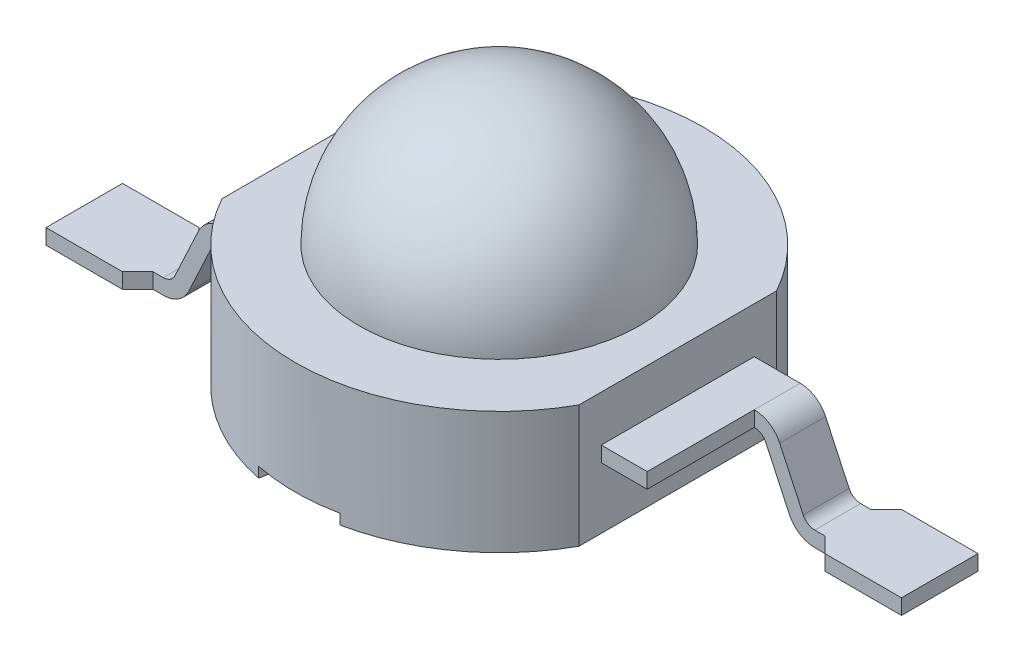
SolidWorks part; units mm, degrees
material "ABS PC"
ref_plane "Front Plane" through (0, 0, 0) normal (0, 0, 1) x (1, 0, 0)
ref_plane "Top Plane" through (0, 0, 0) normal (0, 1, 0) x (1, 0, 0)
ref_plane "Right Plane" through (0, 0, 0) normal (1, 0, 0) x (0, 0, -1)
sketch "Sketch1" plane through (0, 0, 0) normal (0, 1, 0) x (1, 0, 0)
  line L1 (-3.5, 1.9365) -> (3.5, 1.9365) construction
  line L2 (-3.5, 1.9365) -> (-3.5, -1.9365)
  line L3 (-3.5, -1.9365) -> (3.5, -1.9365) construction
  line L4 (3.5, 1.9365) -> (3.5, -1.9365)
  arc A0 (-3.5, -1.9365) -> (3.5, -1.9365) centre (0, 0) ccw
  arc A1 (3.5, 1.9365) -> (-3.5, 1.9365) centre (0, 0) ccw
  dimension "D1" = 8
  dimension "D2" = 7
extrude "Boss-Extrude1" add sketch "Sketch1" along normal blind 2.4
sketch "Sketch2" plane through (0, 0, 0) normal (0, 1, 0) x (1, 0, 0)
  circle A0 centre (0, 0) radius 2.75
  dimension "D1" = 5.5
extrude "Boss-Extrude2" add sketch "Sketch2" against normal blind 0.25
sketch "Sketch3" plane through (0, 2.4, 0) normal (0, 1, 0) x (1, 0, 0)
  circle A0 centre (0, 0) radius 2
  dimension "D1" = 4
extrude "Boss-Extrude3" add sketch "Sketch3" along normal blind 0.3
sketch "Sketch4" plane through (0, 0, 0) normal (0, 0, 1) x (1, 0, 0)
  line L0 (0, 2.4) -> (0, 5.15)
  line L1 (3.5, 2.4) -> (-3.5, 2.4) construction
  line L2 (2.75, 2.4) -> (0, 2.4)
  arc A0 (2.75, 2.4) -> (0, 5.15) centre (0, 2.4) ccw
  dimension "D2" = 2.75
revolve "Revolve1" add sketch "Sketch4" angle 360 about L0
ref_plane "Plane1" through (0, 1.35, 0) normal (0, 1, 0) x (-1, 0, 0)
sketch "Sketch5" plane through (0, 1.35, 0) normal (0, 1, 0) x (-1, 0, 0)
  line L1 (-4.4, 1.5) -> (3.9, 1.5)
  line L2 (-4.4, 1.5) -> (-4.4, -1.5)
  line L3 (-4.4, -1.5) -> (3.9, -1.5)
  line L4 (3.9, 1.5) -> (3.9, -1.5)
  dimension "D1" = 8.3
  dimension "D2" = 3
extrude "Boss-Extrude4" add sketch "Sketch5" along normal mid plane 0.3
sketch "Sketch6" plane through (4.4, 0, 0) normal (1, 0, 0) x (0, 0, -1)
  line L0 (-1.5, 1.2) -> (1.5, 1.2) construction
  line L1 (1.5, 1.5) -> (0.6, 1.5)
  line L2 (1.5, 1.5) -> (1.5, 1.2)
  line L3 (1.5, 1.2) -> (0.6, 1.2)
  line L4 (0.6, 1.5) -> (0.6, 1.2)
  line L5 (1.05, 1.5) -> (1.05, 1.2) construction
  line L6 (1.05, 1.2) -> (0.6, 1.35) construction
  line L7 (0.6, 1.35) -> (1.05, 1.35) construction
  dimension "D1" = 0.9
ref_plane "Plane2" through (0, 0, -1.05) normal (0, 0, 1) x (1, 0, 0)
sketch "Sketch7" plane through (0, 0, -1.05) normal (0, 0, 1) x (1, 0, 0)
  line L0 (4.4, 1.2) -> (4.4, 1.35) construction
  line L1 (4.7625, 1.119) -> (5.2233, 0.131)
  line L2 (3.5, 1.2) -> (4.4, 1.2) construction
  line L3 (-2.75, -0.25) -> (2.75, -0.25) construction
  line L4 (5.5858, -0.1) -> (5.7858, -0.1)
  arc A0 (4.4, 1.35) -> (4.7625, 1.119) centre (4.4, 0.95) cw
  arc A1 (5.2233, 0.131) -> (5.5858, -0.1) centre (5.5858, 0.3) ccw
  point P16 (5.331, -0.1)
  dimension "D5" = 0.4
  dimension "D1" = 115
  dimension "D2" = 0.15
  dimension "D3" = 0.4
  dimension "D4" = 0.2
sweep "Sweep2" add profiles "Sketch6" path "Sketch7"
sketch "Sketch8" plane through (-3.9, 0, 0) normal (-1, 0, 0) x (0, 0, 1)
  line L0 (-1.5, 1.2) -> (1.5, 1.2) construction
  line L1 (1.5, 1.5) -> (0.6, 1.5)
  line L2 (1.5, 1.5) -> (1.5, 1.2)
  line L3 (1.5, 1.2) -> (0.6, 1.2)
  line L4 (0.6, 1.5) -> (0.6, 1.2)
  line L5 (1.05, 1.5) -> (1.05, 1.2) construction
  line L6 (1.05, 1.2) -> (0.6, 1.35) construction
  line L7 (0.6, 1.35) -> (1.05, 1.35) construction
  dimension "D1" = 0.9
ref_plane "Plane3" through (0, 0, 1.05) normal (0, 0, 1) x (1, 0, 0)
sketch "Sketch9" plane through (0, 0, 1.05) normal (0, 0, 1) x (1, 0, 0)
  line L0 (-3.9, 1.5) -> (-3.9, 1.2) construction
  line L1 (-4.2625, 1.119) -> (-4.7233, 0.131)
  line L3 (-3.5, 1.2) -> (-3.9, 1.2) construction
  line L4 (-5.0858, -0.1) -> (-5.2858, -0.1)
  line L5 (-2.75, -0.25) -> (2.75, -0.25) construction
  arc A0 (-3.9, 1.35) -> (-4.2625, 1.119) centre (-3.9, 0.95) ccw
  arc A1 (-4.7233, 0.131) -> (-5.0858, -0.1) centre (-5.0858, 0.3) cw
  dimension "D1" = 0.4
  dimension "D2" = 0.15
  dimension "D3" = 115
  dimension "D4" = 0.2
sweep "Sweep3" add profiles "Sketch8" path "Sketch9"
sketch "Sketch10" plane through (-5.2858, 0, 0) normal (-1, 0, 0) x (0, 0, 1)
  line L0 (1.5, 0.05) -> (0.6, 0.05) construction
  line L1 (0.3, 0.05) -> (1.8, 0.05)
  line L2 (0.3, 0.05) -> (0.3, -0.25)
  line L3 (0.3, -0.25) -> (1.8, -0.25)
  line L4 (1.8, 0.05) -> (1.8, -0.25)
  line L5 (0.6, -0.25) -> (1.5, -0.25) construction
  line L6 (0.6, 0.05) -> (0.6, -0.25) construction
  dimension "D1" = 1.5
  dimension "D2" = 0.3
extrude "Boss-Extrude5" add sketch "Sketch10" along normal blind 1.8
sketch "Sketch11" plane through (5.7858, 0, 0) normal (1, 0, 0) x (0, 0, -1)
  line L0 (1.5, 0.05) -> (0.6, 0.05) construction
  line L1 (0.3, 0.05) -> (1.8, 0.05)
  line L2 (0.3, 0.05) -> (0.3, -0.25)
  line L3 (0.3, -0.25) -> (1.8, -0.25)
  line L4 (1.8, 0.05) -> (1.8, -0.25)
  line L5 (0.6, -0.25) -> (1.5, -0.25) construction
  line L6 (0.6, 0.05) -> (0.6, -0.25) construction
  dimension "D1" = 1.5
  dimension "D2" = 0.3
extrude "Boss-Extrude6" add sketch "Sketch11" along normal blind 1.8
chamfer "Chamfer1" distance 0.3 angle 45 4 edges at (5.7858, -0.1, -0.3) (5.7858, -0.1, -1.8) (-5.2858, -0.1, 0.3) (-5.2858, -0.1, 1.8)
sketch "Sketch12" plane through (0, 0, 0) normal (0, -1, 0) x (1, 0, 0)
  line L0 (0, 4) -> (0, -4) construction
  line L1 (-3.5, 0) -> (3.5, 0) construction
  line L2 (-3.5, -1.9365) -> (-3.5, 1.9365) construction
  line L3 (3.5, 1.5) -> (3.5, -1.5) construction
  arc A0 (3.5, 1.9365) -> (-3.5, 1.9365) centre (0, 0) ccw construction
  arc A1 (-3.5, -1.9365) -> (3.5, -1.9365) centre (0, 0) ccw construction
  circle A2 centre (0, 4) radius 0.8
  circle A3 centre (0, -4) radius 0.8
  dimension "D1" = 1.6
extrude "Cut-Extrude1" cut sketch "Sketch12" against normal blind 0.2
sketch "Sketch13" plane through (-3.5, 0, 0) normal (-1, 0, 0) x (0, 0, 1)
  line L0 (0, 2.4) -> (0, 5.15)
ref_plane "Plane4" through (0, 5.15, 0) normal (0, -1, 0) x (-1, 0, 0)
sketch "Sketch14" plane through (0, 5.15, 0) normal (0, -1, 0) x (-1, 0, 0)
  line L0 (5.3881, 0) -> (-8.9221, 0) construction
